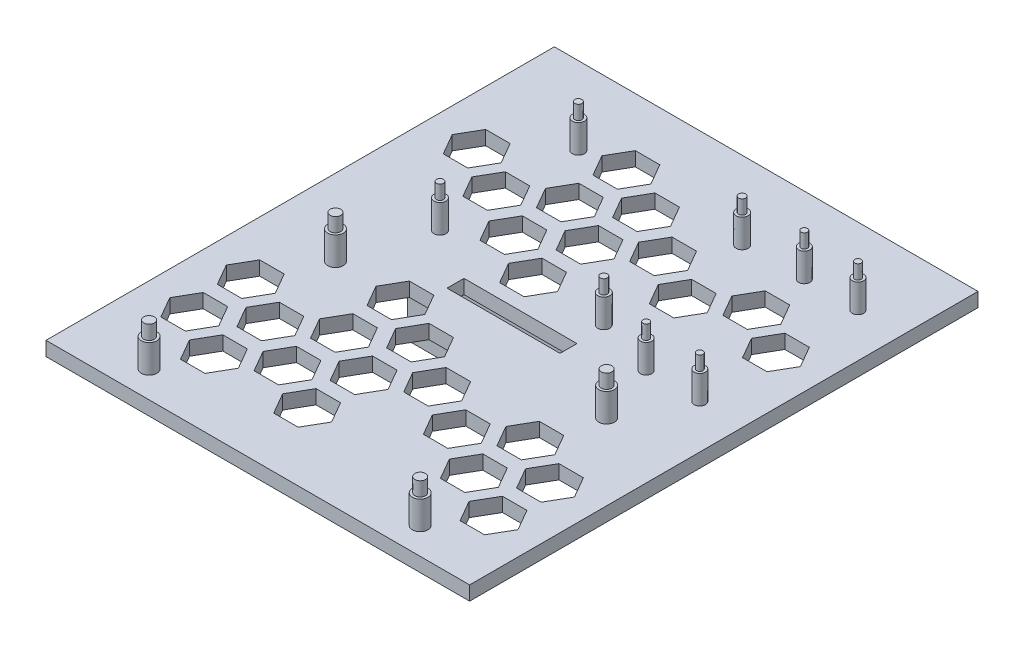
SolidWorks part; units mm, degrees
ref_plane "Front" through (0, 0, 0) normal (0, 0, 1) x (1, 0, 0)
ref_plane "Top" through (0, 0, 0) normal (0, 1, 0) x (1, 0, 0)
ref_plane "Right" through (0, 0, 0) normal (1, 0, 0) x (0, 0, -1)
sketch "Esquisse1" plane through (0, 0, 0) normal (0, 1, 0) x (1, 0, 0)
  line L1 (-31, 6) -> (31, 6)
  line L2 (-31, 6) -> (-31, -6)
  line L3 (-31, -6) -> (31, -6)
  line L4 (31, 6) -> (31, -6)
  line L5 (-31, 6) -> (31, -6) construction
  line L6 (-31, -6) -> (31, 6) construction
  line L7 (-29, 4) -> (29, 4)
  line L8 (-29, 4) -> (-29, -4)
  line L9 (-29, -4) -> (29, -4)
  line L10 (29, 4) -> (29, -4)
  line L11 (-29, 4) -> (29, -4) construction
  line L12 (-29, -4) -> (29, 4) construction
  point P0 (0, 0)
  point P6 (0, 0)
  dimension "D1" = 8
  dimension "D2" = 12
  dimension "D3" = 62
  dimension "D4" = 58
extrude "Boss.-Extru.1" add sketch "Esquisse1" along normal blind 15
sketch "Esquisse2" plane through (0, 0, 6) normal (0, 0, 1) x (1, 0, 0)
  line L0 (-31, 15) -> (31, 15) construction
  line L1 (31, 15) -> (31, 0) construction
  circle A0 centre (0, 9) radius 3.175
  dimension "D1" = 6.35
  dimension "D2" = 6
  dimension "D3" = 31
extrude "Enlèv. mat.-Extru.1" cut sketch "Esquisse2" against normal through all
sketch "Esquisse3" plane through (0, 15, 0) normal (0, 1, 0) x (1, 0, 0)
  line L1 (-75, 90) -> (75, 90)
  line L2 (-75, 90) -> (-75, -90)
  line L3 (-75, -90) -> (75, -90)
  line L4 (75, 90) -> (75, -90)
  line L5 (-75, 90) -> (75, -90) construction
  line L6 (-75, -90) -> (75, 90) construction
  point P0 (0, 0)
  dimension "D1" = 180
  dimension "D2" = 150
extrude "Boss.-Extru.2" add sketch "Esquisse3" along normal blind 5
sketch "Esquisse4" plane through (0, 20, 0) normal (0, 1, 0) x (1, 0, 0)
  line L0 (75, -90) -> (75, 90) construction
  line L1 (-52.5, -85) -> (52.5, -85) construction
  line L2 (-52.5, -85) -> (-52.5, -10) construction
  line L3 (-52.5, -10) -> (52.5, -10) construction
  line L4 (52.5, -85) -> (52.5, -10) construction
  line L5 (-52.5, -85) -> (52.5, -10) construction
  line L6 (-52.5, -10) -> (52.5, -85) construction
  line L7 (-75, -90) -> (75, -90) construction
  line L9 (-61.5, 10) -> (22.5, 10) construction
  line L10 (-61.5, 10) -> (-61.5, 66) construction
  line L11 (-61.5, 66) -> (22.5, 66) construction
  line L12 (22.5, 10) -> (22.5, 66) construction
  line L13 (-61.5, 10) -> (22.5, 66) construction
  line L14 (-61.5, 66) -> (22.5, 10) construction
  line L15 (37.5, 4) -> (62.5, 4) construction
  line L16 (37.5, 4) -> (37.5, 66) construction
  line L17 (37.5, 66) -> (62.5, 66) construction
  line L18 (62.5, 4) -> (62.5, 66) construction
  line L19 (37.5, 4) -> (62.5, 66) construction
  line L20 (37.5, 66) -> (62.5, 4) construction
  line L21 (75, 90) -> (-75, 90) construction
  point P4 (0, -47.5)
  point P10 (0, -90)
  point P15 (-19.5, 38)
  point P21 (50, 35)
  point P22 (75, 0)
  point P24 (0, 90)
  dimension "D1" = 75
  dimension "D2" = 105
  dimension "D3" = 10
  dimension "D4" = 56
  dimension "D5" = 84
  dimension "D6" = 15
  dimension "D7" = 62
  dimension "D8" = 25
  dimension "D9" = 22.5
  dimension "D10" = 10
sketch "Esquisse6" plane through (0, 15, 0) normal (0, -1, 0) x (-1, 0, 0)
  line L0 (-29, -4) -> (-29, 4) construction
  line L1 (20, 3) -> (-20, 3)
  line L2 (20, 3) -> (20, -3)
  line L3 (20, -3) -> (-20, -3)
  line L4 (-20, 3) -> (-20, -3)
  line L5 (20, 3) -> (-20, -3) construction
  line L6 (20, -3) -> (-20, 3) construction
  line L7 (29, -4) -> (-29, -4) construction
  point P4 (0, 0)
  point P8 (-29, 0)
  point P12 (0, -4)
  dimension "D1" = 6
  dimension "D2" = 40
extrude "Enlèv. mat.-Extru.3" cut sketch "Esquisse6" against normal up to next
sketch "Esquisse8" plane through (0, 20, 0) normal (0, 1, 0) x (1, 0, 0)
  line L0 (-61.5, 66) -> (22.5, 66) construction
  line L1 (22.5, 10) -> (22.5, 66) construction
  circle A0 centre (19, 62.5) radius 1.25
  circle A1 centre (19, 13.5) radius 1.25
  circle A2 centre (-39, 62.5) radius 1.25
  circle A3 centre (-39, 13.5) radius 1.25
  dimension "D1" = 2.5
  dimension "D4" = 2.5
  dimension "D6" = 2.5
  dimension "D8" = 2.5
  dimension "D2" = 3.5
  dimension "D3" = 3.5
  dimension "D5" = 49
  dimension "D7" = 58
sketch "Esquisse9" plane through (0, 20, 0) normal (0, 1, 0) x (1, 0, 0)
  line L0 (62.5, 4) -> (62.5, 66) construction
  line L1 (37.5, 66) -> (62.5, 66) construction
  circle A0 centre (59.5, 63) radius 1.125
  circle A1 centre (40.5, 63) radius 1.125
  circle A2 centre (59.5, 7) radius 1.125
  circle A3 centre (40.5, 7) radius 1.125
  dimension "D1" = 2.25
  dimension "D4" = 2.25
  dimension "D6" = 2.25
  dimension "D8" = 2.25
  dimension "D2" = 3
  dimension "D3" = 3
  dimension "D5" = 19
  dimension "D7" = 56
sketch "Esquisse10" plane through (0, 20, 0) normal (0, 1, 0) x (1, 0, 0)
  line L0 (-52.5, -10) -> (52.5, -10) construction
  line L1 (-52.5, -85) -> (-52.5, -10) construction
  circle A0 centre (-48, -14.5) radius 1.875
  circle A1 centre (48, -14.5) radius 1.875
  circle A2 centre (-48, -80.5) radius 1.875
  circle A3 centre (48, -80.5) radius 1.875
  dimension "D1" = 3.75
  dimension "D4" = 3.75
  dimension "D6" = 3.75
  dimension "D8" = 3.75
  dimension "D2" = 4.5
  dimension "D3" = 4.5
  dimension "D5" = 96
  dimension "D7" = 66
sketch "Esquisse11" plane through (0, 20, 0) normal (0, 1, 0) x (1, 0, 0)
  line L0 (-52.5, -10) -> (52.5, -10) construction
  line L1 (-52.5, -85) -> (-52.5, -10) construction
  circle A0 centre (-48, -14.5) radius 2.75
  circle A1 centre (-48, -80.5) radius 2.75
  circle A2 centre (48, -14.5) radius 2.75
  circle A3 centre (48, -80.5) radius 2.75
  dimension "D3" = 5.5
  dimension "D5" = 5.5
  dimension "D6" = 96
  dimension "D7" = 5.5
  dimension "D8" = 5.5
  dimension "D1" = 4.5
  dimension "D2" = 4.5
  dimension "D4" = 66
sketch "Esquisse12" plane through (0, 20, 0) normal (0, 1, 0) x (1, 0, 0)
  line L0 (-61.5, 66) -> (22.5, 66) construction
  line L1 (22.5, 10) -> (22.5, 66) construction
  circle A0 centre (19, 62.5) radius 2.125
  circle A1 centre (19, 13.5) radius 2.125
  circle A2 centre (-39, 62.5) radius 2.125
  circle A3 centre (-39, 13.5) radius 2.125
  dimension "D3" = 4.25
  dimension "D5" = 4.25
  dimension "D7" = 4.25
  dimension "D8" = 4.25
  dimension "D1" = 3.5
  dimension "D2" = 3.5
  dimension "D4" = 49
  dimension "D6" = 58
sketch "Esquisse13" plane through (0, 20, 0) normal (0, 1, 0) x (1, 0, 0)
  line L0 (37.5, 4) -> (62.5, 4) construction
  line L1 (62.5, 4) -> (62.5, 66) construction
  circle A0 centre (59.5, 7) radius 2
  circle A1 centre (59.5, 63) radius 2
  circle A2 centre (40.5, 7) radius 2
  circle A3 centre (40.5, 63) radius 2
  dimension "D3" = 4
  dimension "D4" = 4
  dimension "D6" = 4
  dimension "D8" = 4
  dimension "D1" = 3
  dimension "D2" = 3
  dimension "D5" = 56
  dimension "D7" = 19
extrude "Boss.-Extru.3" add sketch "Esquisse11" along normal blind 10
extrude "Boss.-Extru.4" add sketch "Esquisse13" along normal blind 10
extrude "Boss.-Extru.5" add sketch "Esquisse12" along normal blind 10
extrude "Boss.-Extru.6" add sketch "Esquisse10" along normal blind 15
extrude "Boss.-Extru.7" add sketch "Esquisse9" along normal blind 15
extrude "Boss.-Extru.8" add sketch "Esquisse8" along normal blind 15
sketch "Esquisse14" plane through (0, 20, 0) normal (0, 1, 0) x (1, 0, 0)
  line L0 (-75, -90) -> (75, -90) construction
  line L1 (-53.1699, -62.5) -> (-48.8397, -55)
  line L2 (-48.8397, -55) -> (-53.1699, -47.5)
  line L3 (-53.1699, -47.5) -> (-61.8301, -47.5)
  line L4 (-61.8301, -47.5) -> (-66.1603, -55)
  line L5 (-66.1603, -55) -> (-61.8301, -62.5)
  line L6 (-61.8301, -62.5) -> (-53.1699, -62.5)
  line L7 (-75, 90) -> (-75, -90) construction
  line L9 (-36.7154, -72) -> (-32.3853, -64.5)
  line L10 (-32.3853, -64.5) -> (-36.7154, -57)
  line L11 (-36.7154, -57) -> (-45.3756, -57)
  line L12 (-45.3756, -57) -> (-49.7058, -64.5)
  line L13 (-49.7058, -64.5) -> (-45.3756, -72)
  line L14 (-45.3756, -72) -> (-36.7154, -72)
  line L15 (-48.8397, -55) -> (-45.3756, -57) construction
  circle A0 centre (-57.5, -55) radius 7.5 construction
  circle A1 centre (-41.0455, -64.5) radius 7.5 construction
  point P10 (0, 0)
  point P22 (0, 0)
  dimension "D1" = 15
  dimension "D4" = 15
  dimension "D2" = 35
  dimension "D3" = 17.5
  dimension "D5" = 4
extrude "Enlèv. mat.-Extru.4" cut sketch "Esquisse14" against normal through all
pattern_linear "Répétition linéaire1" count 7 spacing 20 along (0, 0, -1) count 4 spacing 33 along (1, 0, 0) skipping (0, 2), (2, 0), (2, 2), (2, 3), (3, 0), (3, 1), (3, 2), (3, 3), (4, 0), (4, 2), (4, 3), (6, 0), (6, 2), (6, 3) of "Enlèv. mat.-Extru.4"
